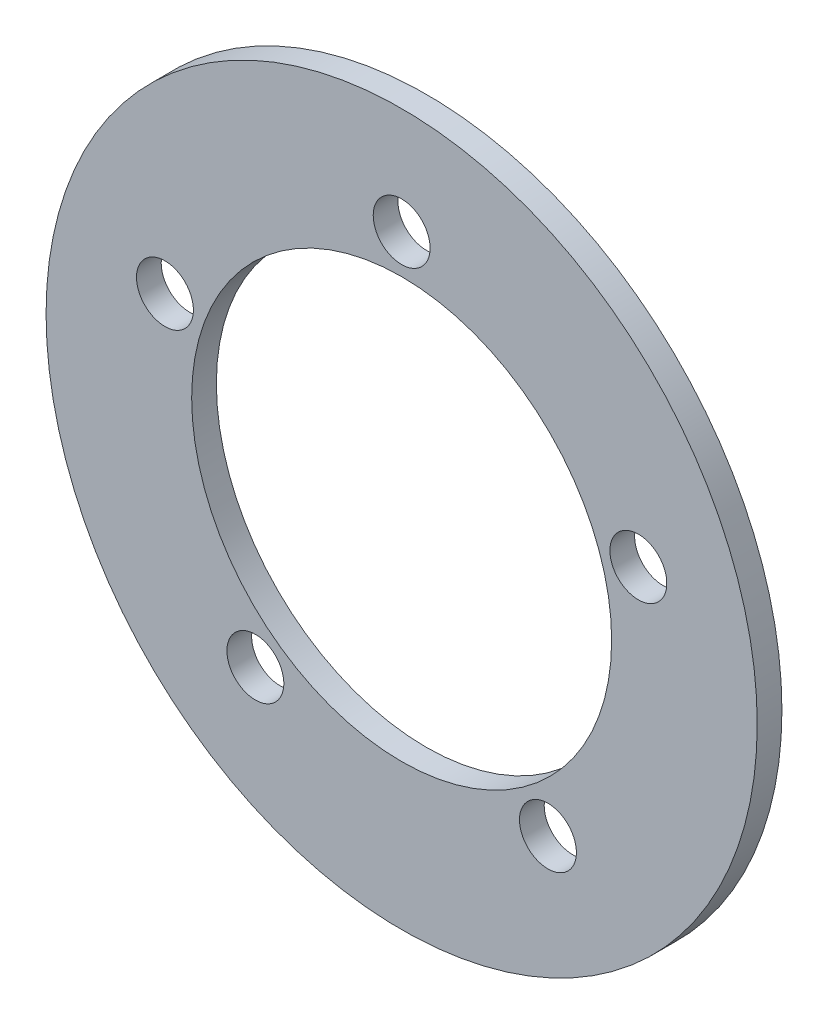
SolidWorks part; units mm, degrees
ref_plane "Front Plane" through (0, 0, 0) normal (0, 0, 1) x (1, 0, 0)
ref_plane "Top Plane" through (0, 0, 0) normal (0, 1, 0) x (1, 0, 0)
ref_plane "Right Plane" through (0, 0, 0) normal (1, 0, 0) x (0, 0, -1)
sketch "Sketch1" plane through (0, 0, -15.24) normal (0, 0, -1) x (-1, 0, 0)
  circle A0 centre (0, 0) radius 13.5 construction
  circle A1 centre (0, 0) radius 13.5
  circle A2 centre (0, 0) radius 22.86
  circle A3 centre (15.2169, 4.9443) radius 1.8288 construction
  circle A4 centre (9.4046, -12.9443) radius 1.8288 construction
  circle A5 centre (-9.4046, -12.9443) radius 1.8288 construction
  circle A6 centre (-15.2169, 4.9443) radius 1.8288 construction
  circle A7 centre (0, 16) radius 1.8288 construction
  circle A8 centre (15.2169, 4.9443) radius 1.8288
  circle A9 centre (9.4046, -12.9443) radius 1.8288
  circle A10 centre (-9.4046, -12.9443) radius 1.8288
  circle A11 centre (-15.2169, 4.9443) radius 1.8288
  circle A12 centre (0, 16) radius 1.8288
  dimension "D1" = 45.72
extrude "Boss-Extrude1" add sketch "Sketch1" along normal blind 1.5875
